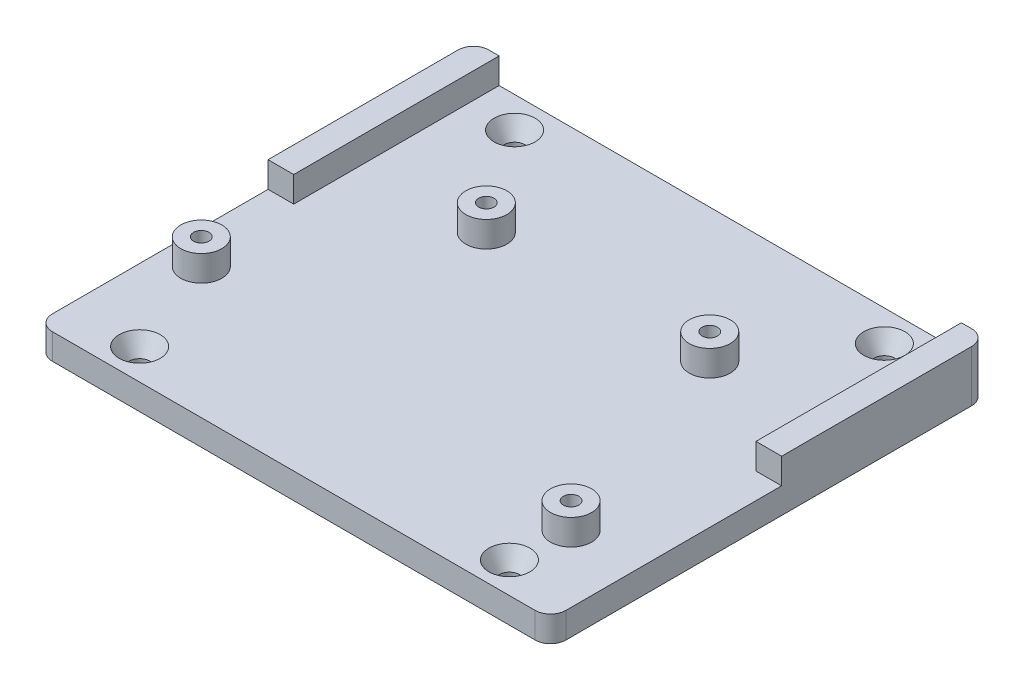
SolidWorks part; units mm, degrees
ref_plane "Alzado" through (0, 0, 0) normal (0, 0, 1) x (1, 0, 0)
ref_plane "Planta" through (0, 0, 0) normal (0, 1, 0) x (1, 0, 0)
ref_plane "Vista lateral" through (0, 0, 0) normal (1, 0, 0) x (0, 0, -1)
sketch "Croquis1" plane through (0, 0, 0) normal (0, 1, 0) x (1, 0, 0)
  line L0 (-36, 36.5) -> (36, -36.5) construction
  line L2 (-50, 42.5) -> (-50, -42.5)
  line L3 (-50, -42.5) -> (50, -42.5)
  line L4 (50, 42.5) -> (50, -42.5)
  line L5 (-50, 42.5) -> (50, -42.5) construction
  line L6 (-50, -42.5) -> (50, 42.5) construction
  line L7 (-36, -36.5) -> (36, 36.5) construction
  line L8 (-50, 42.5) -> (50, 42.5)
  circle A0 centre (-36, -36.5) radius 2
  circle A1 centre (-36, 36.5) radius 2
  circle A2 centre (36, 36.5) radius 2
  circle A3 centre (36, -36.5) radius 2
  point P0 (0, 0)
  point P14 (0, 0)
  point P15 (0, 0)
  point P17 (0, 0)
  dimension "D6" = 4
  dimension "D1" = 100
  dimension "D2" = 85
  dimension "D3" = 73
  dimension "D4" = 72
  dimension "D5" = 73
extrude "Saliente-Extruir2" add sketch "Croquis1" along normal blind 5
chamfer "Chaflán1" distance 2 angle 60 4 edges at (-36, 5, 38.5) (36, 5, 38.5) (36, 5, -34.5) (-36, 5, -34.5) first distance on face at (36, 5, -34.5)
sketch "Croquis3" plane through (0, 5, 0) normal (0, 1, 0) x (1, 0, 0)
  line L0 (-50, -42.5) -> (50, -42.5) construction
  line L1 (-50, 42.5) -> (-50, -42.5) construction
  circle A0 centre (-43.5, -17) radius 4
  circle A1 centre (37, -25.5) radius 4
  circle A2 centre (22, 16.5) radius 4
  circle A3 centre (-21.5, 16.5) radius 4
  circle A4 centre (-21.5, 16.5) radius 1.5
  circle A5 centre (-43.5, -17) radius 1.5
  circle A6 centre (22, 16.5) radius 1.5
  circle A7 centre (37, -25.5) radius 1.5
  dimension "D3" = 8
  dimension "D10" = 3
  dimension "D1" = 25.5
  dimension "D2" = 6.5
  dimension "D4" = 28.5
  dimension "D5" = 59
  dimension "D6" = 87
  dimension "D7" = 17
  dimension "D8" = 72
  dimension "D9" = 59
extrude "Saliente-Extruir3" add sketch "Croquis3" along normal blind 5
sketch "Croquis4" plane through (0, 5, 0) normal (0, 1, 0) x (1, 0, 0)
  line L1 (-50, 42.5) -> (-45, 42.5)
  line L2 (-50, 42.5) -> (-50, 2.5)
  line L3 (-50, 2.5) -> (-45, 2.5)
  line L4 (-45, 42.5) -> (-45, 2.5)
  line L5 (50, 42.5) -> (45, 42.5)
  line L6 (50, 42.5) -> (50, 2.5)
  line L7 (50, 2.5) -> (45, 2.5)
  line L8 (45, 42.5) -> (45, 2.5)
  point P4 (0, 0)
  dimension "D1" = 5
  dimension "D2" = 5
  dimension "D3" = 40
extrude "Saliente-Extruir4" add sketch "Croquis4" along normal up to surface (5 mm away) up to face at (-21.5, 10, -12.5)
fillet "Redondeo1" radius 3 4 edges at (50, 2.5, 42.5) (-50, 5, -42.5) (-50, 2.5, 42.5) (50, 5, -42.5)
